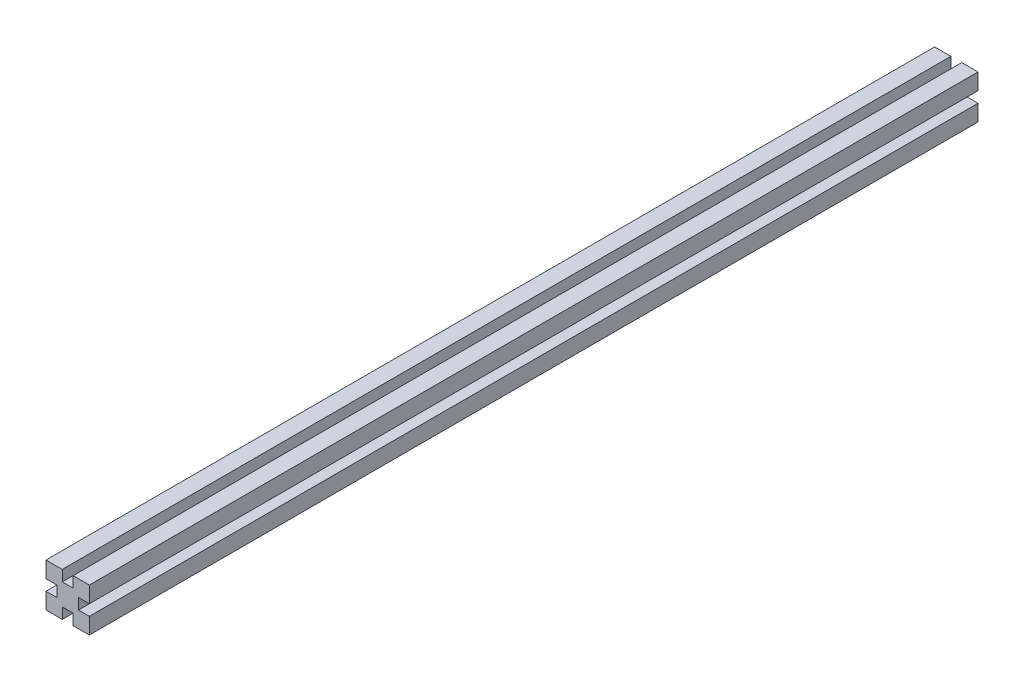
SolidWorks part; units mm, degrees
ref_plane "Front Plane" through (0, 0, 0) normal (0, 0, 1) x (1, 0, 0)
ref_plane "Top Plane" through (0, 0, 0) normal (0, 1, 0) x (1, 0, 0)
ref_plane "Right Plane" through (0, 0, 0) normal (1, 0, 0) x (0, 0, -1)
sketch "Sketch1" plane through (0, 0, 0) normal (0, 0, 1) x (1, 0, 0)
  line L1 (-10, 10) -> (10, 10)
  line L2 (-10, 10) -> (-10, -10)
  line L3 (-10, -10) -> (10, -10)
  line L4 (10, 10) -> (10, -10)
  line L5 (-10, 10) -> (10, -10) construction
  line L6 (-10, -10) -> (10, 10) construction
  line L7 (-2.5, 15) -> (2.5, 15)
  line L8 (-2.5, 15) -> (-2.5, 5)
  line L9 (-2.5, 5) -> (2.5, 5)
  line L10 (2.5, 15) -> (2.5, 5)
  line L11 (-2.5, 15) -> (2.5, 5) construction
  line L12 (-2.5, 5) -> (2.5, 15) construction
  point P0 (0, 0)
  point P6 (0, 10)
  dimension "D1" = 20
  dimension "D2" = 20
  dimension "D3" = 5
  dimension "D4" = 10
extrude "Boss-Extrude1" add sketch "Sketch1" against normal blind 410 contours L1 L10 L9 L8 L2 L3 L4 | L10 L1 L8 L9 region at (0, -0.5, 0) region at (0, 7.5, 0)
extrude "Cut-Extrude1" cut sketch "Sketch1<3>" against normal blind 645 contours L8 L9 L10 L7
sketch "Sketch1<3>" plane through (0, 0, 0) normal (0, 0, 1) x (1, 0, 0) same geometry as "Sketch1"
ref_axis "Axis1" through (0, 0, -256.4154) along (0, 0, -1)
pattern_circular "CirPattern1" count 4 over 360 about axis through (0, 0, -256.4154) along (0, 0, -1) of "Cut-Extrude1"
